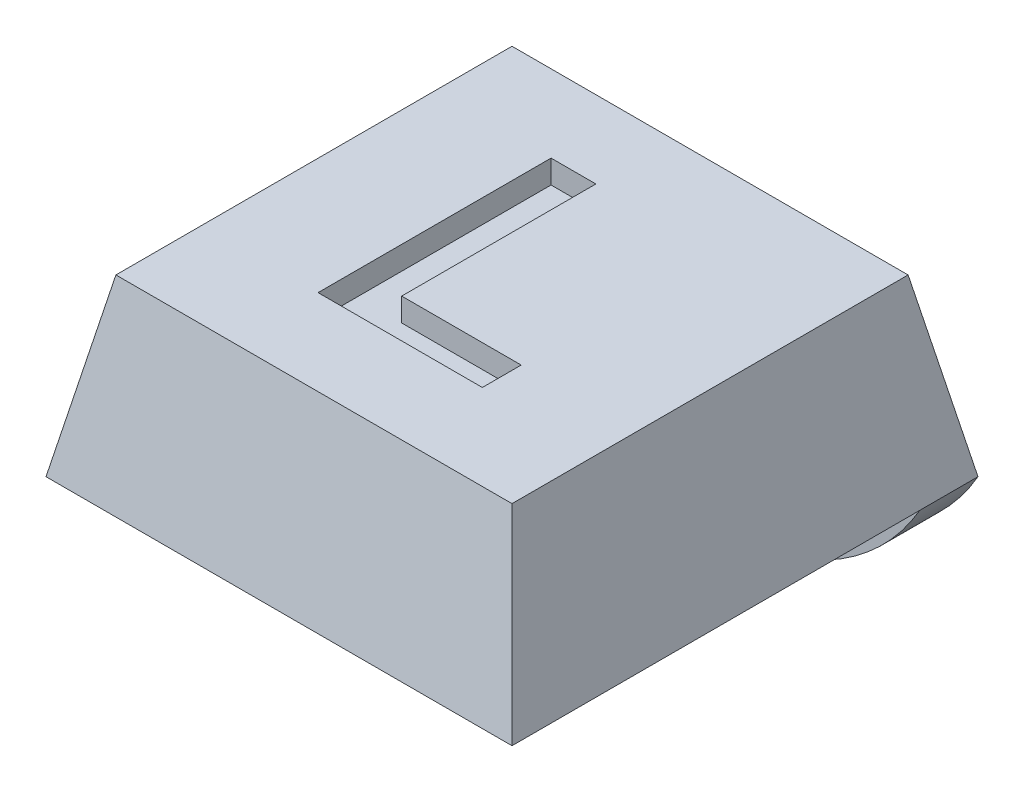
SolidWorks part; units mm, degrees
ref_plane "Front Plane" through (0, 0, 0) normal (0, 0, 1) x (1, 0, 0)
ref_plane "Top Plane" through (0, 0, 0) normal (0, 1, 0) x (1, 0, 0)
ref_plane "Right Plane" through (0, 0, 0) normal (1, 0, 0) x (0, 0, -1)
sketch "Sketch1" plane through (0, 0, 0) normal (0, 1, 0) x (1, 0, 0)
  line L1 (0, 0) -> (8, 0)
  line L2 (0, 0) -> (0, 8)
  line L3 (0, 8) -> (8, 8)
  line L4 (8, 0) -> (8, 8)
  dimension "D1" = 8
  dimension "D2" = 8
extrude "Boss-Extrude1" add sketch "Sketch1" along normal blind 3
sketch "Sketch2" plane through (0, 0, 0) normal (0, 0, 1) x (1, 0, 0)
  line L0 (0, 0) -> (0.6, 3)
  line L1 (0, 3) -> (8, 3) construction
  line L2 (0.6, 3) -> (0, 3)
  line L3 (0, 3) -> (0, 0)
  line L4 (8, 0) -> (7.4, 3)
  line L5 (7.4, 3) -> (8, 3)
  line L6 (8, 3) -> (8, 0)
  dimension "D1" = 0.6
  dimension "D2" = 0.6
extrude "Cut-Extrude1" cut sketch "Sketch2" against normal through all both and the other way through all
sketch "Sketch3" plane through (0, 0, 0) normal (1, 0, 0) x (0, 0, -1)
  line L0 (0, 0) -> (0.6, 3)
  line L1 (8, 3) -> (0, 3) construction
  line L2 (0.6, 3) -> (0, 3)
  line L3 (0, 3) -> (0, 0)
  line L4 (8, 3) -> (7.4, 3)
  line L5 (7.4, 3) -> (8, 0)
  line L6 (8, 3) -> (8, 0)
  dimension "D1" = 0.6
  dimension "D2" = 0.6
extrude "Cut-Extrude2" cut sketch "Sketch3" along normal blind 11
sketch "Sketch4" plane through (0, 0, 0) normal (0, -1, 0) x (1, 0, 0)
  line L0 (8, 0) -> (8, -8) construction
  line L3 (0, 0) -> (8, 0) construction
  circle A0 centre (4, -3.75) radius 1.8
  dimension "D1" = 3.6
  dimension "D2" = 4
  dimension "D3" = 3.75
extrude "Cut-Extrude3" cut sketch "Sketch4" against normal blind 0.8
sketch "Sketch5" plane through (0, 0, 0) normal (0, -1, 0) x (1, 0, 0)
  line L0 (8, 0) -> (8, -8) construction
  line L1 (0, -8) -> (8, -8)
  line L2 (0, -8) -> (0, -7)
  line L3 (0, -7) -> (8, -7)
  line L4 (8, -8) -> (8, -7)
  dimension "D1" = 1
extrude "Boss-Extrude2" add sketch "Sketch5" along normal blind 2
fillet "Fillet1" radius 4 2 edges at (8, -2, -7.5) (0, -2, -7.5)
sketch "Sketch6" plane through (0, 3, 0) normal (0, 1, 0) x (1, 0, 0)
  text T0 "L" font "Arial" height 4
extrude "Cut-Extrude4" cut sketch "Sketch6" against normal blind 0.4
